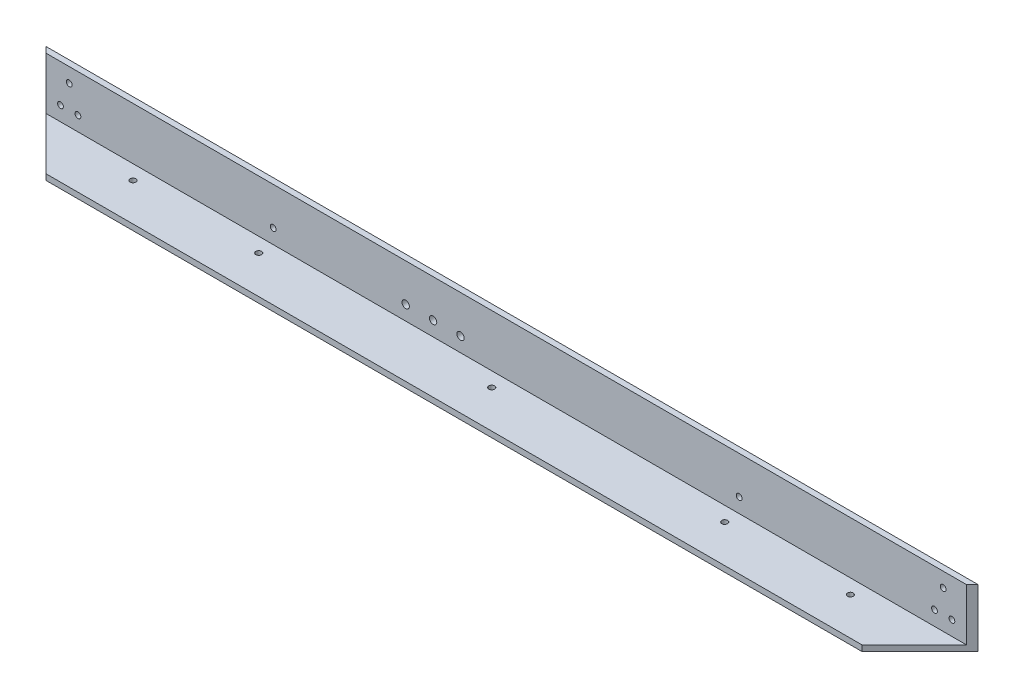
SolidWorks part; units mm, degrees
ref_plane "Front Plane" through (0, 0, 0) normal (0, 0, 1) x (1, 0, 0)
ref_plane "Top Plane" through (0, 0, 0) normal (0, 1, 0) x (1, 0, 0)
ref_plane "Right Plane" through (0, 0, 0) normal (1, 0, 0) x (0, 0, -1)
sketch "Sketch1" plane through (0, 0, 0) normal (1, 0, 0) x (0, 0, -1)
  line L0 (0, 0) -> (-31.75, 0)
  line L1 (-31.75, 0) -> (-31.75, 3.175)
  line L2 (-31.75, 3.175) -> (-3.175, 3.175)
  line L3 (-3.175, 3.175) -> (-3.175, 31.75)
  line L4 (-3.175, 31.75) -> (0, 31.75)
  line L5 (0, 31.75) -> (0, 0)
  dimension "LHeight" = 31.75
  dimension "LWidth" = 31.75
  dimension "LMaterialThickness" = 3.175
  dimension "D1" = 28.575
  dimension "D2" = 28.575
  dimension "D3" = 3.175
extrude "Boss-Extrude1" add sketch "Sketch1" along normal blind 510
chamfer "Chamfer6" distance 31.75 angle 45 1 edges at (510, 1.5875, 31.75)
chamfer "Chamfer7" distance 31.75 angle 45 1 edges at (0, 1.5875, 31.75)
sketch "TopHoles-Sketch3" plane through (0, 3.175, 0) normal (0, 1, 0) x (1, 0, 0)
  line L0 (510, 0) -> (0, 0) construction
  circle A9 centre (451.2625, -11.1125) radius 1.5875
  circle A10 centre (58.7375, -11.1125) radius 1.5875
  circle A13 centre (127.5, -11.1125) radius 1.5875
  circle A14 centre (255, -11.1125) radius 1.5875
  circle A15 centre (382.5, -11.1125) radius 1.5875
  dimension "D5" = 3.175
  dimension "D8" = 127.5
  dimension "D10" = 127.5
  dimension "D11" = 127.5
  dimension "D13" = 68.7625
  dimension "D2" = 11.1125
  dimension "D3" = 58.7375
  dimension "D4" = 58.7375
extrude "TopHoles-Cut-Extrude2" cut sketch "TopHoles-Sketch3" against normal through all
sketch "BackHoles-Sketch4" plane through (0, 0, 3.175) normal (0, 0, 1) x (1, 0, 0)
  line L0 (0, 0) -> (0, 31.75) construction
  line L1 (510, 0) -> (510, 31.75) construction
  line L2 (478.25, 0) -> (31.75, 0) construction
  line L3 (510, 31.75) -> (0, 31.75) construction
  line L7 (510, 0) -> (0, 0) construction
  circle A3 centre (494.125, 23.8125) radius 1.5875
  circle A4 centre (15.875, 23.8125) radius 1.5875
  circle A6 centre (11.1125, 11.1125) radius 1.5875
  circle A7 centre (20.6375, 11.1125) radius 1.5875
  circle A8 centre (489.3625, 11.1125) radius 1.5875
  circle A9 centre (498.8875, 11.1125) radius 1.5875
  circle A10 centre (200, 11.1125) radius 2
  circle A11 centre (215, 11.1125) radius 2
  circle A12 centre (230, 11.1125) radius 2
  circle A13 centre (127.5, 11.1125) radius 1.5875
  circle A14 centre (382.5, 11.1125) radius 1.5875
  dimension "D11" = 4
  dimension "D2" = 3.175
  dimension "D7" = 11.1125
  dimension "D6" = 15.875
  dimension "D5" = 15.875
  dimension "D8" = 215
  dimension "D9" = 15
  dimension "D10" = 15
  dimension "D12" = 11.1125
  dimension "D13" = 127.5
  dimension "D14" = 127.5
  dimension "D4" = 7.9375
  dimension "D15" = 11.1125
  dimension "D3" = 11.1125
  dimension "D16" = 20.6375
  dimension "D17" = 20.6375
extrude "BackHoles-Cut-Extrude3" cut sketch "BackHoles-Sketch4" against normal through all
equation "\"TopRailWidth\"= 1.25in"
equation "\"TopRailHeight\"= 1.25in"
equation "\"RailThickness\"= .125in'Spec"
equation "\"SideRailHoleY1FromEdge\"= \"HoleOffsetFromEdge\""
equation "\"SideRailHoleX1FromSide\"= \"HoleOffsetFromSide\""
equation "\"VSWidth\"= 1.25in'Spec"
equation "\"HoleOffsetFromEdge\"= \"RailThickness\" * 2.5"
equation "\"HoleOffsetFromSide\"= \"RailThickness\" * 3.5"
equation "\"SideRailHoleX2FromSide\"= \"VSWidth\" - \"HoleOffsetFromEdge\" - \"RailThickness\"'Equals 20.6375"
equation "\"FasteningHoleDiameter\"= .125in"
equation "\"SideRailHoleY2FromSide\"= \"HoleOffsetFromSide\""
equation "\"LWidth@Sketch1\"=\"TopRailWidth\""
equation "\"LHeight@Sketch1\"=\"TopRailHeight\""
equation "\"LMaterialThickness@Sketch1\"=\"RailThickness\""
equation "\"D1@Boss-Extrude1\"= \"FrontBackRailLength\""
equation "\"FrontBackRailLength\"= 510mm"
equation "\"D7@BackHoles-Sketch4\"=\"SideRailHoleY2FromSide\""
equation "\"D1@Chamfer6\"=\"TopRailWidth\""
equation "\"D1@Chamfer7\"=\"TopRailWidth\""
equation "\"D6@BackHoles-Sketch4\"=\"VSMidSideRailHoleXFromSideToCenter\" - \"RailThickness\""
equation "\"D5@BackHoles-Sketch4\"=\"VSMidSideRailHoleXFromSideToCenter\" - \"RailThickness\""
equation "\"D8@BackHoles-Sketch4\"=\"FrontBackRailLength\"/2 - 40mm"
equation "\"TopHoleY1FromSide\"= \"HoleOffsetFromSide\""
equation "\"TopCBLength\"= \"TopRailWidth\" * 2'Equals 63.5"
equation "\"FrontOrBackEnclosureOffsets\"= \"FrontBackRailLength\" / 4"
equation "\"D8@TopHoles-Sketch3\"=\"FrontOrBackEnclosureOffsets\""
equation "\"D11@TopHoles-Sketch3\"=\"FrontOrBackEnclosureOffsets\""
equation "\"D10@TopHoles-Sketch3\"=\"FrontOrBackEnclosureOffsets\""
equation "\"D13@BackHoles-Sketch4\"=\"FrontOrBackEnclosureOffsets\""
equation "\"D14@BackHoles-Sketch4\"=\"FrontOrBackEnclosureOffsets\""
equation "\"D2@BackHoles-Sketch4\"=\"FasteningHoleDiameter\""
equation "\"D4@BackHoles-Sketch4\"=\"SideRailHoleY1FromEdge\""
equation "\"D15@BackHoles-Sketch4\"=\"SideRailHoleX1FromSide\""
equation "\"D3@BackHoles-Sketch4\"=\"SideRailHoleX1FromSide\""
equation "\"FrontOrBackCornerEnclosureOffset\"= \"RailThickness\" + \"TopCBLength\" - \"HoleOffsetFromEdge\"'Equals 58.7375"
equation "\"D2@TopHoles-Sketch3\"=\"TopHoleY1FromSide\""
equation "\"D3@TopHoles-Sketch3\"=\"FrontOrBackCornerEnclosureOffset\""
equation "\"D4@TopHoles-Sketch3\"=\"FrontOrBackCornerEnclosureOffset\""
equation "\"D5@TopHoles-Sketch3\"=\"FasteningHoleDiameter\""
equation "\"VSMidSideRailHoleXFromSideToCenter\"= \"RailThickness\" * 6"
equation "\"D16@BackHoles-Sketch4\"=\"SideRailHoleX2FromSide\""
equation "\"D17@BackHoles-Sketch4\"=\"SideRailHoleX2FromSide\""
